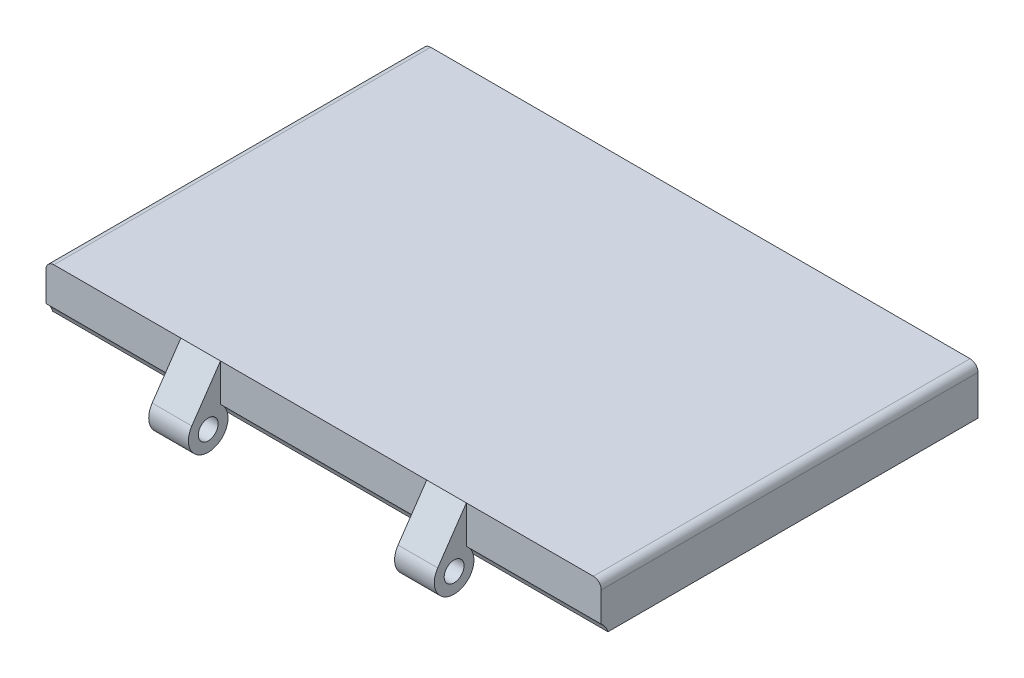
SolidWorks part; units mm, degrees
ref_plane "前视基准面" through (0, 0, 0) normal (0, 0, 1) x (1, 0, 0)
ref_plane "上视基准面" through (0, 0, 0) normal (0, 1, 0) x (1, 0, 0)
ref_plane "右视基准面" through (0, 0, 0) normal (1, 0, 0) x (0, 0, -1)
sketch "草图19" plane through (0, 0, 0) normal (0, 0, 1) x (1, 0, 0)
  line L0 (0, 1.8966) -> (0, -36.3685) construction
  line L1 (-35, 1.8966) -> (35, 1.8966)
  line L2 (-35, 1.8966) -> (-35, -1.8966)
  line L3 (-33, -0.1034) -> (33, -0.1034)
  line L4 (35, 1.8966) -> (35, -1.8966)
  line L5 (-35, 1.8966) -> (35, -1.8966) construction
  line L6 (-35, -1.8966) -> (35, 1.8966) construction
  line L8 (-35, -1.8966) -> (-35, -4.1034)
  line L9 (-35, -4.1034) -> (-33, -4.1034)
  line L10 (-33, -0.1034) -> (-33, -4.1034)
  line L11 (33, -0.1034) -> (33, -4.1034)
  line L12 (35, -4.1034) -> (33, -4.1034)
  line L13 (35, -1.8966) -> (35, -4.1034)
  point P0 (0, 0)
  dimension "D1" = 70
  dimension "D2" = 2
  dimension "D3" = 6
  dimension "D4" = 2
extrude "凸台-拉伸2" add sketch "草图19" against normal mid plane 47.5
sketch "草图21" plane through (0, 0, 23.75) normal (0, 0, 1) x (1, 0, 0)
  line L0 (-33, -4.1034) -> (33, -4.1034)
  line L8 (35, -4.1034) -> (35, 1.8966)
  line L9 (35, 1.8966) -> (-35, 1.8966)
  line L10 (-35, 1.8966) -> (-35, -4.1034)
  line L11 (-35, -4.1034) -> (-33, -4.1034)
  line L12 (-33, -4.1034) -> (-33, -0.1034)
  line L13 (-33, -0.1034) -> (33, -0.1034)
  line L14 (33, -0.1034) -> (33, -4.1034)
  line L15 (33, -4.1034) -> (35, -4.1034)
  line L16 (35, -4.1034) -> (35, 1.8966)
  line L17 (35, 1.8966) -> (-35, 1.8966)
  line L18 (-35, 1.8966) -> (-35, -4.1034)
  line L19 (-35, -4.1034) -> (-33, -4.1034)
  line L23 (33, -4.1034) -> (35, -4.1034)
  dimension "D1" = 0
extrude "凸台-拉伸4" add sketch "草图21" against normal blind 2
sketch "草图30" plane through (-35, 0, 0) normal (-1, 0, 0) x (0, 0, 1)
  line L4 (24, -11.9389) -> (27.4543, -6.0718)
  line L5 (24, -6.9389) -> (24, -11.9389)
  arc A4 (22.9, -4.1034) -> (24, -6.9389) centre (25.3, -4.8034) ccw
  arc A5 (27.4543, -6.0718) -> (22.9, -4.1034) centre (25.3, -4.8034) ccw
extrude "切除-拉伸2" cut sketch "草图30" against normal through all
ref_plane "基准面1" through (-18, 0, 0) normal (-1, 0, 0) x (0, 0, 1)
sketch "草图32" plane through (-18, 0, 0) normal (-1, 0, 0) x (0, 0, 1)
  line L0 (23.75, 1.8966) -> (27.3642, -3.3931)
  line L1 (23.75, 1.8966) -> (23.75, -2.8419)
  line L2 (-23.75, 1.8966) -> (23.75, 1.8966) construction
  arc A0 (23.75, -2.8419) -> (27.3642, -3.3931) centre (25.3, -4.8034) ccw
extrude "凸台-拉伸6" add sketch "草图32" against normal blind 5
mirror "镜向2" about plane through (0, 0, 0) normal (1, 0, 0) of "凸台-拉伸6"
sketch "草图33" plane through (-18, 0, 0) normal (-1, 0, 0) x (0, 0, 1)
  circle A0 centre (25.3, -4.8034) radius 1.25
  dimension "D1" = 2.5
extrude "切除-拉伸3" cut sketch "草图33" against normal through all
sketch "草图34" plane through (0, 0, -23.75) normal (0, 0, -1) x (-1, 0, 0)
  line L0 (-33, -4.1034) -> (-35, -4.1034) construction
  line L1 (-34.5, -4.1034) -> (34.2, -4.1034)
  line L2 (-34.5, -4.1034) -> (-34.5, 0.3966)
  line L3 (-33.5, 1.3966) -> (33.2, 1.3966)
  line L4 (34.2, -4.1034) -> (34.2, 0.3966)
  line L5 (-35, -4.1034) -> (-35, 1.8966) construction
  line L6 (35, 1.8966) -> (35, -4.1034) construction
  line L7 (-35, 1.8966) -> (35, 1.8966) construction
  arc A0 (33.2, 1.3966) -> (34.2, 0.3966) centre (33.2, 0.3966) cw
  arc A1 (-34.5, 0.3966) -> (-33.5, 1.3966) centre (-33.5, 0.3966) cw
  dimension "D4" = 1
  dimension "D1" = 0.5
  dimension "D2" = 0.8
  dimension "D3" = 0.5
extrude "切除-拉伸4" cut sketch "草图34" against normal blind 3
ref_plane "基准面5" through (16, 0, 0) normal (-1, 0, 0) x (0, 0, 1)
sketch "草图42" plane through (16, 0, 0) normal (-1, 0, 0) x (0, 0, 1)
  line L0 (-20.75, -0.1034) -> (21.75, -0.1034) construction
  line L1 (13.15, -0.1034) -> (7.65, -0.1034)
  line L2 (13.15, -0.1034) -> (13.15, -8.1034)
  line L3 (12.15, -9.1034) -> (8.65, -9.1034)
  line L4 (7.65, -0.1034) -> (7.65, -8.1034)
  line L5 (10.4, -0.1034) -> (10.4, -9.1034) construction
  line L6 (21.75, -0.1034) -> (21.75, -4.1034) construction
  arc A0 (13.15, -8.1034) -> (12.15, -9.1034) centre (12.15, -8.1034) cw
  arc A1 (8.65, -9.1034) -> (7.65, -8.1034) centre (8.65, -8.1034) cw
  point P12 (13.15, -9.1034)
  point P15 (7.65, -9.1034)
  dimension "D4" = 1
  dimension "D1" = 11.35
  dimension "D2" = 5.5
  dimension "D3" = 9
extrude "凸台-拉伸9" add sketch "草图42" against normal blind 4
sketch "草图43" plane through (20, 0, 0) normal (1, 0, 0) x (0, 0, -1)
  line L0 (-10.4, -9.1034) -> (-10.4, 1.8966) construction
  line L1 (-8.65, -9.1034) -> (-12.15, -9.1034) construction
  line L2 (23.75, 1.8966) -> (-23.75, 1.8966) construction
  line L3 (20.75, -0.1034) -> (-21.75, -0.1034) construction
  circle A0 centre (-10.4, -6.1034) radius 1.5
  dimension "D1" = 6
  dimension "D2" = 3
extrude "切除-拉伸7" cut sketch "草图43" against normal up to next
fillet "圆角2" radius 1 2 edges at (35, 1.8966, 0) (-35, 1.8966, 0)
fillet "圆角3" radius 2 4 edges at (20, -0.1034, 10.4) (18, -0.1034, 13.15) (16, -0.1034, 10.4) (18, -0.1034, 7.65)
thread "螺纹线1" pitch 0.5 method cut profile "螺纹线轮廓2" start angle 0, offset 0.5, length 0, pitch 0.5, diameter 3
ref_plane "基准面7" through (16.5, -6.1034, 8.9) normal (0, -1, 0) x (0, 0, -1)
sketch "螺纹线轮廓2" plane through (16.5, -6.1034, 8.9) normal (0, -1, 0) x (0, 0, -1)
  line L0 (0, 0) -> (0, 0.5) construction
  line L1 (0, 0) -> (0.2706, 0.1562)
  line L2 (0.2706, 0.1562) -> (0.2706, 0.2187)
  line L3 (0.2706, 0.2187) -> (0, 0.375)
  line L4 (0.2706, 0.1875) -> (0, 0.1875) construction
  line L11 (0, 0) -> (0, 0.375)
  point P2 (0, 0)
  dimension "Pitch" = 0.5
  dimension "Profile_Angle" = 60
  dimension "Profile_Land" = 0.0625
  dimension "Profile_Height" = 0.2706
fillet "圆角4" radius 0.5 14 edges at (15.4142, -0.6892, 7.0642) (15.4142, -0.6892, 13.7358) (16, -5.1034, 13.15) (16, -8.8105, 12.8571) (16, -9.1034, 10.4) (16, -8.8105, 7.9429) (20.5858, -0.6892, 7.0642) (20.5858, -0.6892, 13.7358) (20, -5.1034, 13.15) (20, -8.8105, 12.8571) (20, -9.1034, 10.4) (20, -8.8105, 7.9429) (16, -5.1034, 7.65) (20, -5.1034, 7.65)
sketch "折弯-线1" plane through (0, 0, 0) normal (0, 1, 0) x (1, 0, 0)
sketch "边界框1" plane through (0, 0, 0) normal (0, 1, 0) x (1, 0, 0)
